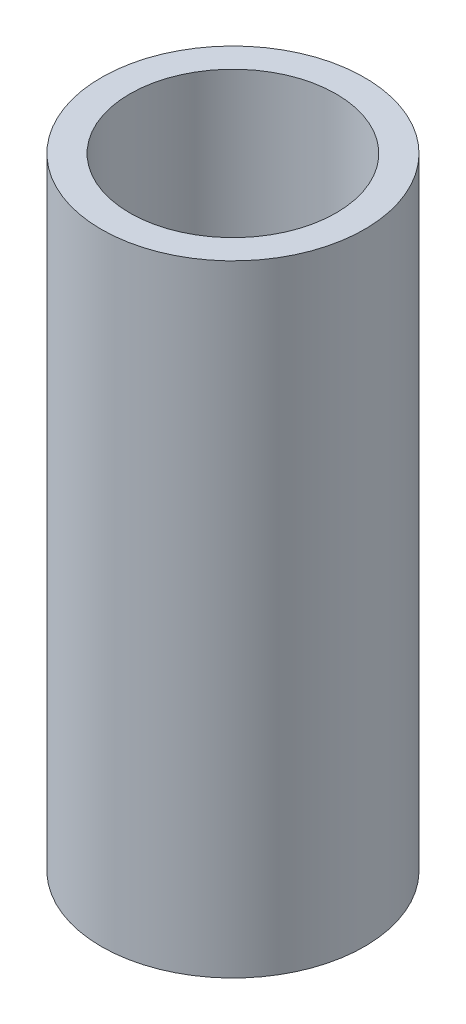
SolidWorks part; units mm, degrees
ref_plane "Front Plane" through (0, 0, 0) normal (0, 0, 1) x (1, 0, 0)
ref_plane "Top Plane" through (0, 0, 0) normal (0, 1, 0) x (1, 0, 0)
ref_plane "Right Plane" through (0, 0, 0) normal (1, 0, 0) x (0, 0, -1)
sketch "Sketch1" plane through (0, 0, 0) normal (0, 1, 0) x (1, 0, 0)
  circle A0 centre (0, 0) radius 6.25
extrude "Boss-Extrude1" add sketch "Sketch1" along normal blind 29.5
sketch "Sketch2" plane through (0, 29.5, 0) normal (0, 1, 0) x (1, 0, 0)
  circle A0 centre (0, 0) radius 4.9
extrude "Cut-Extrude1" cut sketch "Sketch2" against normal through all
